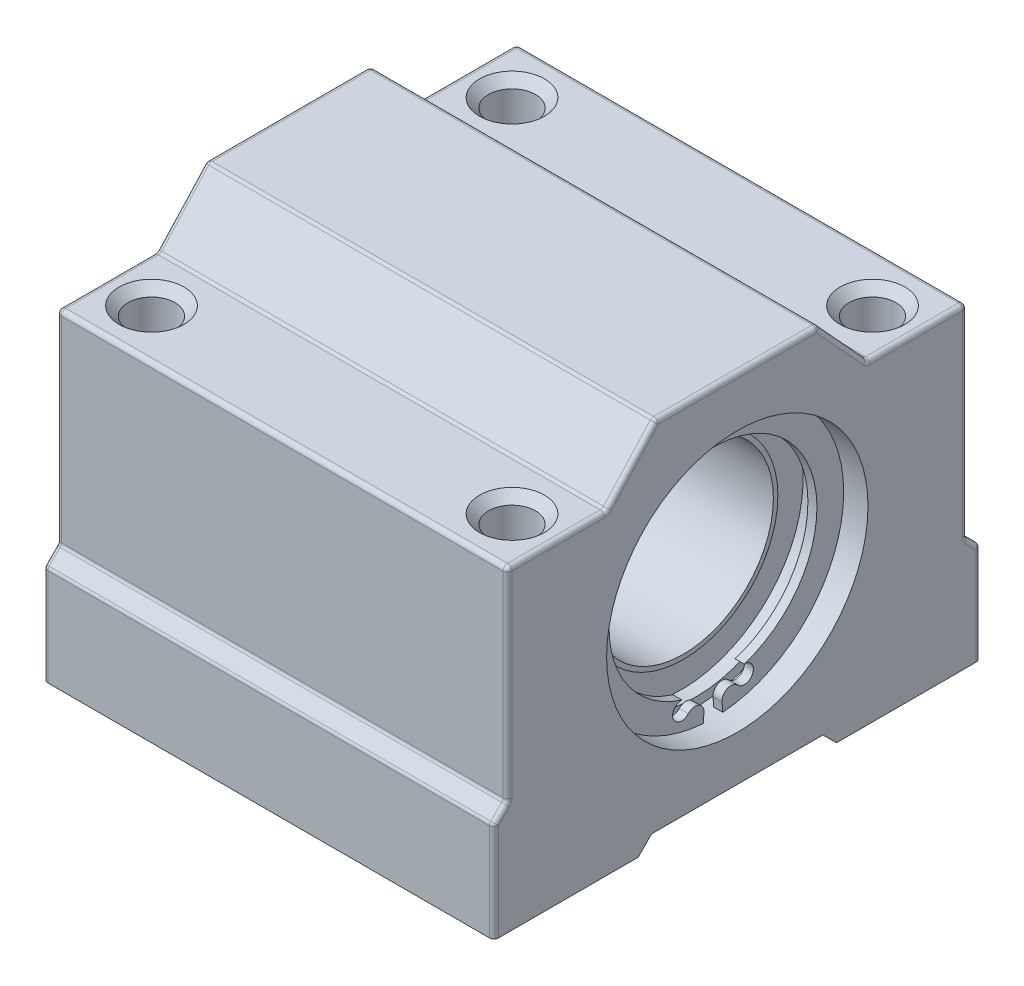
SolidWorks part; units mm, degrees
ref_plane "Front Plane" through (0, 0, 0) normal (0, 0, 1) x (1, 0, 0)
ref_plane "Top Plane" through (0, 0, 0) normal (0, 1, 0) x (1, 0, 0)
ref_plane "Right Plane" through (0, 0, 0) normal (1, 0, 0) x (0, 0, -1)
sketch "Sketch1" plane through (0, 0, 0) normal (1, 0, 0) x (0, 0, -1)
  line L1 (-11, -21) -> (-9.5, -19.5)
  line L2 (-9.5, -19.5) -> (9.5, -19.5)
  line L3 (9.5, -19.5) -> (11, -21)
  line L4 (11, -21) -> (27, -21)
  line L6 (27, -10) -> (25.5, -8.5)
  line L8 (25.5, 14) -> (14.5, 14)
  line L9 (14.5, 14) -> (9, 20)
  line L10 (9, 20) -> (-9, 20)
  line L11 (-9, 20) -> (-14.5, 14)
  line L12 (-14.5, 14) -> (-25.5, 14)
  line L15 (-27, -10) -> (-27, -21)
  line L16 (0, -19.5) -> (0, 20) construction
  line L17 (-16.278, 0) -> (14.0247, 0) construction
  line L18 (-27, -21) -> (-11, -21)
  line L19 (27, -10) -> (27, -21)
  line L20 (-25.5, -8.5) -> (-25.5, 14)
  line L21 (25.5, -8.5) -> (25.5, 14)
  line L22 (-20, 14) -> (-20, -21) construction
  line L23 (-20, -21) -> (20, 14) construction
  line L24 (20, 14) -> (20, -21) construction
  line L25 (-27, -10) -> (-25.5, -8.5)
  line L26 (-14.5, 0) -> (14.5, 0) construction
  circle A0 centre (0, 0) radius 14.5
  circle A1 centre (0, 0) radius 13.5
  circle A2 centre (0, 0) radius 10
  point P18 (0, 20)
  point P23 (0, 0)
  dimension "D12" = 20
  dimension "D1" = 54
  dimension "D2" = 35
  dimension "D3" = 21
  dimension "D5" = 41
  dimension "D6" = 40
  dimension "D4" = 11
  dimension "D7" = 1.5
  dimension "D8" = 18
  dimension "D9" = 1.5
  dimension "D10" = 16
  dimension "D11" = 1
extrude "Boss-Extrude1" add sketch "Sketch1" along normal blind 50 contours L25 L15 L18 L1 L2 L3 L4 L19 L6 L21 L8 L9 L10 L11 L12 L20 A0 region at (0, -20.322, 19)
extrude "Extrude-Thin1" add sketch "Sketch1<4>" along normal blind 43.5 from offset 0.5 separate body thin contours A2 thin type one direction wall 0.5
sketch "Sketch1<4>" plane through (0, 0, 0) normal (1, 0, 0) x (0, 0, -1) same geometry as "Sketch1"
extrude "Boss-Extrude2" add sketch "Sketch1<5>" along normal blind 43 from offset 0.8 contours A1 A2 region at (0, 0, 13.1182)
sketch "Sketch1<5>" plane through (0, 0, 0) normal (1, 0, 0) x (0, 0, -1) same geometry as "Sketch1"
extrude "Boss-Extrude3" add sketch "Sketch1<6>" along normal blind 45 from offset 0.3 contours A0 A1 region at (0, 0, 14.0899)
sketch "Sketch1<6>" plane through (0, 0, 0) normal (1, 0, 0) x (0, 0, -1) same geometry as "Sketch1"
ref_plane "Plane1" through (45.3, 0, 0) normal (1, 0, 0) x (0, 0, -1)
sketch "Sketch3" plane through (45.3, 0, 0) normal (1, 0, 0) x (0, 0, -1)
  line L0 (0, 0) -> (0, -50000) construction
  line L1 (-1.0062, -13.4624) -> (-1.0808, -14.4597)
  line L2 (1.0062, -13.4624) -> (1.0808, -14.4597)
  circle A0 centre (0, 0) radius 14.5 construction
  arc A1 (1.0808, -14.4597) -> (-1.0808, -14.4597) centre (0, 0) ccw
  circle A2 centre (0, 0) radius 13.5 construction
  arc A3 (0, -13.5) -> (1.0062, -13.4624) centre (0, 0) ccw
  arc A4 (-1.0062, -13.4624) -> (-2.74, -12.6784) centre (-2, -13.351) ccw
  circle A5 centre (-2, -13.351) radius 0.25
  arc A6 (-2.2469, -13.3117) -> (-1.7524, -13.3858) centre (0, 0) ccw
  arc A7 (-2.74, -12.6784) -> (-3.4569, -11.0061) centre (-3.48, -12.0058) cw
  arc A8 (2.74, -12.6784) -> (3.4569, -11.0061) centre (3.48, -12.0058) ccw
  circle A10 centre (2, -13.351) radius 0.25
  arc A11 (1.0062, -13.4624) -> (2.74, -12.6784) centre (2, -13.351) cw
  arc A13 (3.4569, -11.0061) -> (-3.4569, -11.0061) centre (0, 0) ccw
  point P12 (-1.1793, -6.3921)
  dimension "D1" = 0.5
  dimension "D2" = 2
  dimension "D3" = 1
  dimension "D4" = 2
extrude "Boss-Extrude4" add sketch "Sketch3" along normal blind 1 from offset 1 contours A11 A8 A13 A7 A4 L1 A1 L2
fillet "Fillet1" radius 0.5 32 edges at (25, -8.5, -25.5) (25, -8.5, 25.5) (25, -10, 27) (25, -10, -27) (25, 14, -14.5) (25, 14, 14.5) (25, 20, 9) (25, 20, -9) (25, 14, -25.5) (25, 14, 25.5) (50, 17, -11.75) (50, 17, 11.75) (50, 2.75, 25.5) (0, -9.25, 26.25) (0, 17, 11.75) (50, -9.25, -26.25) (50, -15.5, -27) (50, 2.75, -25.5) (50, 20, 0) (50, 14, -20) (50, 14, 20) (50, -9.25, 26.25) (50, -15.5, 27) (0, -15.5, -27) (0, -9.25, -26.25) (0, 2.75, -25.5) (0, 17, -11.75) (0, 14, -20) (0, 20, 0) (0, -15.5, 27) (0, 2.75, 25.5) (0, 14, 20)
sketch "Sketch4" plane through (0, -21, 0) normal (0, -1, 0) x (1, 0, 0)
  line L0 (25, 27) -> (25, -27) construction
  line L1 (49.5, 27) -> (0.5, 27) construction
  line L2 (49.5, -27) -> (0.5, -27) construction
  line L4 (-4.9444, 20) -> (27.0918, 20) construction
  line L6 (0, 0) -> (36.1646, 0) construction
  circle A0 centre (5, 20) radius 2.6
  circle A1 centre (45, 20) radius 2.6
  circle A2 centre (45, -20) radius 2.6
  circle A3 centre (5, -20) radius 2.6
  dimension "D2" = 5.2
  dimension "D1" = 20
  dimension "D3" = 40
extrude "Cut-Extrude3" cut sketch "Sketch4" against normal through all
chamfer "Chamfer1" distance 1 angle 45 6 edges at (45, 14, -22.6) (5, 14, -22.6) (5, 14, 17.4) (45, 14, 17.4) (45, -21, 22.6) (5, -21, 17.4)
equation "\"D1@Boss-Extrude2\"= \"D1@Boss-Extrude1\" - 2 - 5"
equation "\"D1@Boss-Extrude3\"= \"D1@Boss-Extrude1\" - 5"
equation "\"D1@Sketch4\"= \"D6@Sketch1\" / 2"
equation "\"D1@Extrude-Thin1\"= \"D1@Boss-Extrude3\" - 1.5"
